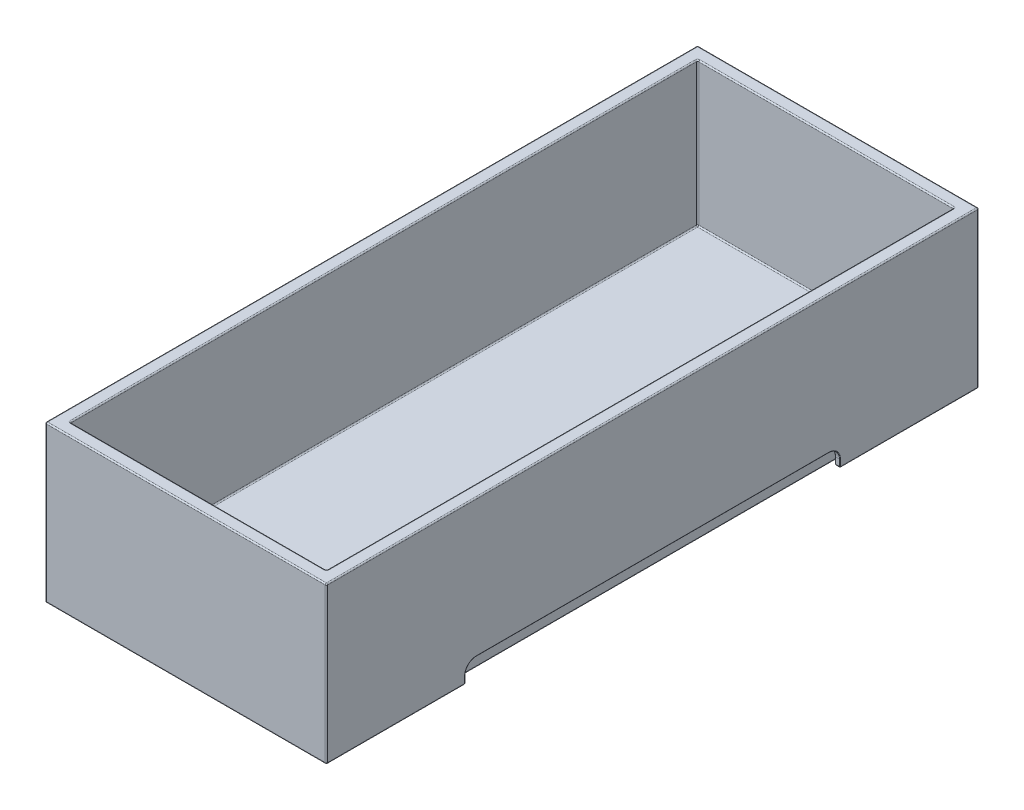
SolidWorks part; units mm, degrees
ref_plane "Front Plane" through (0, 0, 0) normal (0, 0, 1) x (1, 0, 0)
ref_plane "Top Plane" through (0, 0, 0) normal (0, 1, 0) x (1, 0, 0)
ref_plane "Right Plane" through (0, 0, 0) normal (1, 0, 0) x (0, 0, -1)
sketch "Sketch1" plane through (0, 0, 0) normal (1, 0, 0) x (0, 0, -1)
  line L1 (522, -125) -> (-522, -125)
  line L2 (522, -125) -> (522, 125)
  line L3 (522, 125) -> (-522, 125)
  line L4 (-522, -125) -> (-522, 125)
  line L5 (522, -125) -> (-522, 125) construction
  line L6 (522, 125) -> (-522, -125) construction
  point P0 (0, 0)
  dimension "D1" = 1044
  dimension "D2" = 250
extrude "Boss-Extrude1" add sketch "Sketch1" against normal blind 450
sketch "Sketch2" plane through (0, 125, 0) normal (0, 1, 0) x (1, 0, 0)
  line L0 (-450, 522) -> (0, 522) construction
  line L1 (-430, 502) -> (-20, 502)
  line L2 (-430, 502) -> (-430, -502)
  line L3 (-430, -502) -> (-20, -502)
  line L4 (-20, 502) -> (-20, -502)
  line L5 (-450, 522) -> (-450, -522) construction
  line L6 (-450, -522) -> (0, -522) construction
  line L7 (0, 522) -> (0, -522) construction
  dimension "D1" = 20
  dimension "D2" = 20
  dimension "D3" = 20
  dimension "D4" = 20
extrude "Cut-Extrude1" cut sketch "Sketch2" against normal offset from surface (230 mm away) 20 up to face at (-225, -125, 0)
sketch "Sketch3" plane through (0, 0, 0) normal (1, 0, 0) x (0, 0, -1)
  line L0 (-522, -125) -> (522, -125) construction
  line L1 (-300, -125) -> (300, -125)
  line L2 (-300, -125) -> (-300, -113)
  line L3 (-282, -95) -> (282, -95)
  line L4 (300, -125) -> (300, -113)
  arc A0 (282, -95) -> (300, -113) centre (282, -113) cw
  arc A1 (-300, -113) -> (-282, -95) centre (-282, -113) cw
  point P4 (0, -125)
  point P10 (300, -95)
  point P13 (-300, -95)
  dimension "D3" = 18
  dimension "D1" = 30
  dimension "D2" = 600
extrude "Cut-Extrude2" cut sketch "Sketch3" against normal blind 15
sketch "Sketch4" plane through (-15, 0, 0) normal (1, 0, 0) x (0, 0, -1)
  line L0 (-300, -125) -> (300, -125) construction
  line L1 (-310, -125) -> (310, -125)
  line L2 (-310, -125) -> (-310, -108)
  line L3 (-287, -85) -> (287, -85)
  line L4 (310, -125) -> (310, -108)
  arc A0 (287, -85) -> (310, -108) centre (287, -108) cw
  arc A1 (-310, -108) -> (-287, -85) centre (-287, -108) cw
  point P6 (0, -85)
  point P10 (310, -85)
  point P13 (-310, -85)
  dimension "D3" = 23
  dimension "D1" = 620
  dimension "D2" = 40
extrude "Cut-Extrude3" cut sketch "Sketch4" along normal blind 7
fillet "Fillet1" radius 1 20 edges at (-8, -116.5, -310) (-8, -91.7365, -303.2635) (-8, -85, 0) (-8, -116.5, 310) (0, -119, -300) (0, -100.2721, -294.7279) (0, -119, 300) (0, -100.2721, 294.7279) (-8, -119, -300) (-8, -100.2721, -294.7279) (-8, -119, 300) (-8, -100.2721, 294.7279) (-15, -116.5, -310) (-15, -91.7365, -303.2635) (-15, -116.5, 310) (-15, -91.7365, 303.2635) (-8, -91.7365, 303.2635) (0, -95, 0) (-8, -95, 0) (-15, -85, 0)
fillet "Fillet2" radius 2 40 edges at (-225, 125, -502) (-430, 10, -502) (-430, 125, 0) (-20, 10, -502) (-20, 125, 0) (-430, 10, 502) (-20, 10, 502) (-225, 125, 502) (-225, -105, -502) (-20, -105, 0) (-225, -105, 502) (-430, -105, 0) (-450, 125, 0) (-225, 125, -522) (-450, 0, -522) (-450, 0, 522) (-225, 125, 522) (-225, -125, -522) (-450, -125, 0) (-225, -125, 522) (-0.2929, -125, 300.2929) (-4, -125, 300) (-7.7071, -125, 300.2929) (-8, -125, 305) (-8.2929, -125, 309.7071) (-11.5, -125, 310) (-14.7071, -125, 309.7071) (-15, -125, 0) (-14.7071, -125, -309.7071) (-11.5, -125, -310) (-8.2929, -125, -309.7071) (-8, -125, -305) (-7.7071, -125, -300.2929) (-4, -125, -300) (-0.2929, -125, -300.2929) (0, -125, 411.5) (0, 0, 522) (0, 125, 0) (0, 0, -522) (0, -125, -411.5)
